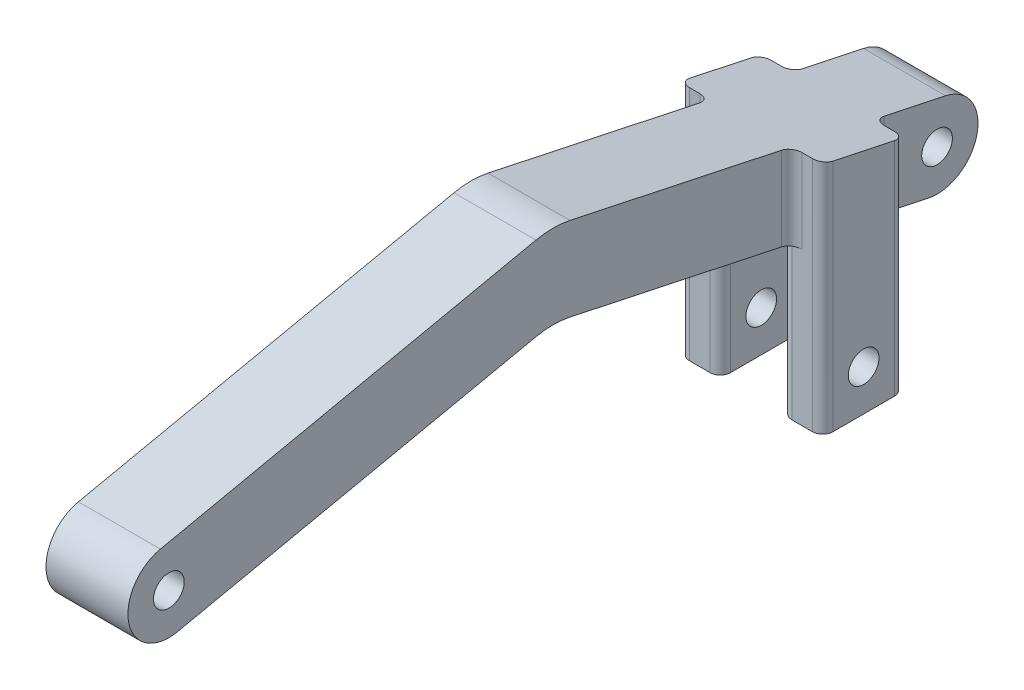
SolidWorks part; units mm, degrees
ref_plane "Alzado" through (0, 0, 0) normal (0, 0, 1) x (1, 0, 0)
ref_plane "Planta" through (0, 0, 0) normal (0, 1, 0) x (1, 0, 0)
ref_plane "Vista lateral" through (0, 0, 0) normal (1, 0, 0) x (0, 0, -1)
sketch "Croquis1" plane through (0, 0, 0) normal (1, 0, 0) x (0, 0, -1)
  line L0 (-38.3316, 3.9126) -> (0, 12.0602) construction
  line L9 (0, 12.0602) -> (38.3316, 3.9126) construction
  line L10 (-36.6684, -3.9126) -> (0, 3.8815) construction
  line L15 (-37.5, 0) -> (37.5, 0) construction
  line L16 (0, 3.8815) -> (36.6684, -3.9126) construction
  line L17 (-38.3316, 3.9126) -> (-1.6633, 11.7067)
  line L18 (1.6633, 11.7067) -> (38.3316, 3.9126)
  line L19 (-36.6684, -3.9126) -> (-1.6633, 3.528)
  line L20 (1.6633, 3.528) -> (36.6684, -3.9126)
  circle A2 centre (-37.5, 0) radius 1.5
  circle A4 centre (37.5, 0) radius 1.5
  arc A7 (-38.3316, 3.9126) -> (-36.6684, -3.9126) centre (-37.5, 0) ccw
  arc A8 (36.6684, -3.9126) -> (38.3316, 3.9126) centre (37.5, 0) ccw
  arc A9 (-1.6633, 11.7067) -> (1.6633, 11.7067) centre (0, 3.8815) cw
  arc A10 (-1.6633, 3.528) -> (1.6633, 3.528) centre (0, -4.2972) cw
  point P0 (0, 0)
  point P1 (0, 0)
  dimension "D4" = 3
  dimension "D2" = 8
  dimension "D5" = 8
  dimension "D1" = 75
  dimension "D3" = 12
  dimension "D7" = 12
extrude "Saliente-Extruir1" add sketch "Croquis1" along normal mid plane 8
sketch "Croquis3" plane through (0, 0, 0) normal (0, 1, 0) x (1, 0, 0)
  line L1 (4, 38.3316) -> (-4, 38.3316) construction
  line L2 (-4, 31.3316) -> (-7, 31.3316)
  line L3 (-4, 31.3316) -> (-4, 23.3316)
  line L4 (-4, 23.3316) -> (-7, 23.3316)
  line L5 (-7, 31.3316) -> (-7, 23.3316)
  line L10 (0, 0) -> (0, 38.3316) construction
  line L13 (4, 23.3316) -> (7, 23.3316)
  line L14 (7, 31.3316) -> (7, 23.3316)
  line L15 (4, 31.3316) -> (7, 31.3316)
  line L16 (4, 31.3316) -> (4, 23.3316)
  line L17 (-4, 38.3316) -> (-4, 1.6633) construction
  point P10 (-7, 27.3316)
  point P11 (-4, 27.3316)
  dimension "D1" = 3
  dimension "D2" = 8
  dimension "D3" = 7
extrude "Saliente-Extruir2" add sketch "Croquis3" against normal up to surface and the other way up to surface up to face at (0, -0.1923, -19.1658) other way up to face at (0, 7.8096, -19.9975)
sketch "Croquis4" plane through (0, 0, 0) normal (0, -1, 0) x (1, 0, 0)
  line L25 (-7, -23.3316) -> (7, -23.3316)
  line L26 (-7, -23.3316) -> (-7, -31.3316)
  line L27 (-7, -31.3316) -> (7, -31.3316)
  line L28 (7, -23.3316) -> (7, -31.3316)
extrude "Saliente-Extruir3" add sketch "Croquis4" along normal blind 16
sketch "Croquis7" plane through (0, -16, 0) normal (0, -1, 0) x (1, 0, 0)
  line L1 (3, -31.3316) -> (-3, -31.3316)
  line L2 (3, -31.3316) -> (3, -23.3316)
  line L3 (3, -23.3316) -> (-3, -23.3316)
  line L4 (-3, -31.3316) -> (-3, -23.3316)
  line L5 (3, -31.3316) -> (-3, -23.3316) construction
  line L6 (3, -23.3316) -> (-3, -31.3316) construction
  line L8 (4, -23.3316) -> (-4, -23.3316) construction
  line L9 (-7, -31.3316) -> (7, -31.3316) construction
  point P0 (0, -27.3316)
  dimension "D1" = 6
extrude "Cortar-Extruir2" cut sketch "Croquis7" against normal up to surface (13.2218 mm away) up to face at (0, 1.2251, -12.4975)
fillet "Redondeo1" radius 1 12 edges at (4, 3.0116, -23.3316) (4, 1.3111, -31.3316) (-4, 3.0116, -23.3316) (-4, 1.3111, -31.3316) (3, -9.3891, -31.3316) (-3, -9.3891, -31.3316) (-3, -8.5389, -23.3316) (3, -8.5389, -23.3316) (7, -4.4495, -23.3316) (7, -5.2998, -31.3316) (-7, -5.2998, -31.3316) (-7, -4.4495, -23.3316)
sketch "Croquis6" plane through (0, 0, 0) normal (1, 0, 0) x (0, 0, -1)
  line L1 (30.3316, -16) -> (24.3316, -16) construction
  circle A0 centre (27.3316, -12) radius 1.5
  point P2 (0, 0)
  point P8 (27.3316, -16)
  dimension "D2" = 3
  dimension "D1" = 12
extrude "Cortar-Extruir1" cut sketch "Croquis6" against normal through all both and the other way through all
